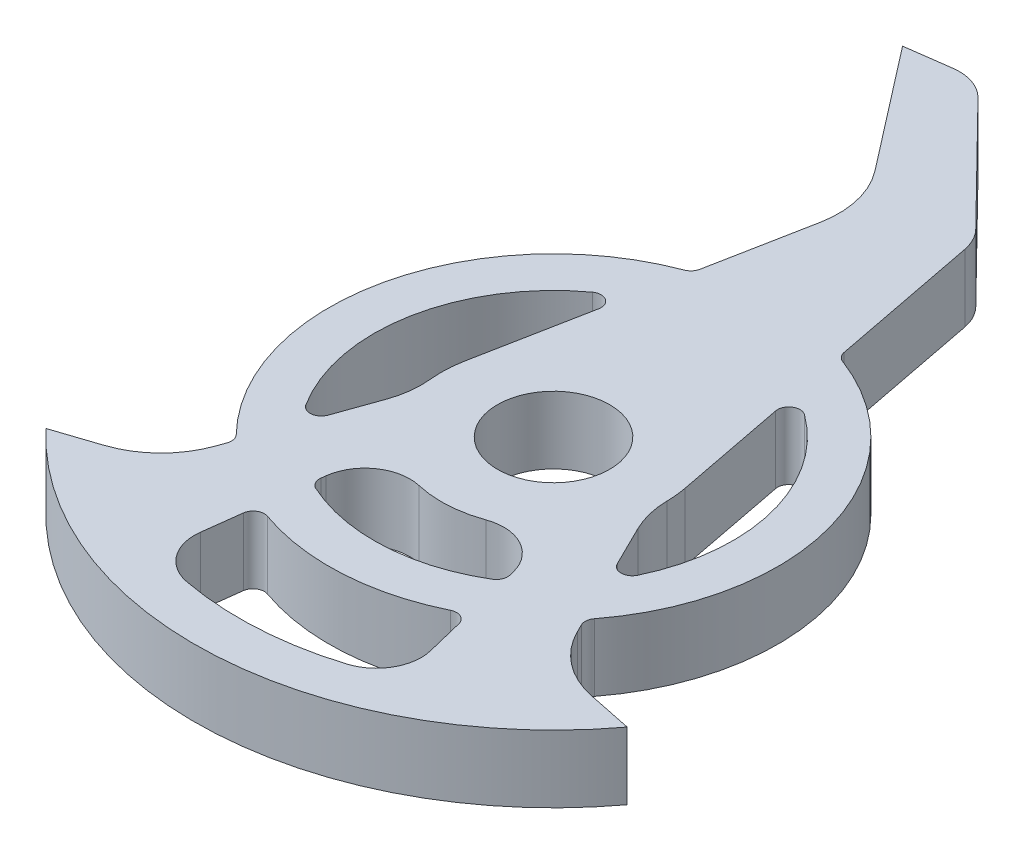
SolidWorks part; units mm, degrees
material "AISI Type A2 Tool Steel"
ref_plane "Front Plane" through (0, 0, 0) normal (0, 0, 1) x (1, 0, 0)
ref_plane "Top Plane" through (0, 0, 0) normal (0, 1, 0) x (1, 0, 0)
ref_plane "Right Plane" through (0, 0, 0) normal (1, 0, 0) x (0, 0, -1)
other "Center of Mass"
other "Bounding Box"
ref_plane "Default Plane" through (-8.9266, -12.7485, 0) normal (-0.1736, 0.9848, 0) x (0.9848, 0.1736, 0)
sketch "Sketch1" plane through (0, 0, 0) normal (0, 1, 0) x (1, 0, 0)
  line L0 (-15.5865, 3.0126) -> (-6.35, 50.8)
  line L1 (-6.35, 50.8) -> (-23.2013, 72.582)
  line L2 (15.5865, 3.0126) -> (6.35, 50.8)
  line L4 (-6.35, 50.8) -> (6.35, 50.8) construction
  line L5 (0, 50.8) -> (0, 0) construction
  line L6 (-23.2013, 72.582) -> (0, 0) construction
  line L7 (-23.2013, 72.582) -> (-13.7628, 73.8626)
  line L8 (-13.7628, 73.8626) -> (5.7363, 53.975)
  line L9 (5.7363, 53.975) -> (6.35, 50.8)
  circle A0 centre (0, 0) radius 7.9375
  arc A1 (-15.5865, 3.0126) -> (15.5865, 3.0126) centre (0, 0) ccw
  circle A2 centre (0, 0) radius 76.2 construction
  arc A4 (15.5865, 3.0126) -> (-15.5865, 3.0126) centre (0, 0) ccw construction
  dimension "D1" = 15.875
  dimension "D2" = 152.4
  dimension "D3" = 31.75
  dimension "D4" = 3.175
  dimension "D5" = 12.7
  dimension "D6" = 50.8
  dimension "D7" = 20
  dimension "D8" = 9.525
  dimension "D9" = 60
extrude "Boss-Extrude1" add sketch "Sketch1" along normal mid plane 9.525
fillet "Fillet6" radius 6.35 2 edges at (-13.7628, 0, -73.8626) (5.7363, 0, -53.975)
fillet "Fillet9" radius 12.7 1 edges at (-6.35, 0, -50.8)
sketch "Sketch4" plane through (0, 4.7625, 0) normal (0, 1, 0) x (1, 0, 0)
  circle A0 centre (0, 0) radius 31.75
  circle A1 centre (0, 0) radius 25.4
  dimension "D1" = 63.5
  dimension "D2" = 6.35
extrude "Boss-Extrude4" add sketch "Sketch4" against normal up to surface (9.525 mm away) up to face at (-6.3228, -4.7625, -45.9675)
sketch "Sketch2" plane through (0, 4.7625, 0) normal (0, 1, 0) x (1, 0, 0)
  line L0 (0, 0) -> (-1.4202, 24.3492) construction
  line L1 (-15.343, -4.0753) -> (-24.8926, -30.8684)
  line L2 (-24.8926, -30.8684) -> (-36.9477, -34.8642)
  line L3 (15.7127, -2.2639) -> (28.3126, -27.7651)
  line L4 (28.3126, -27.7651) -> (40.7504, -30.3323)
  line L5 (2.958, -50.7138) -> (0, 0) construction
  line L6 (-36.9477, -34.8642) -> (0, 0) construction
  line L7 (0, 0) -> (40.7504, -30.3323) construction
  line L8 (-36.9477, -34.8642) -> (1.9014, -32.5982) construction
  line L9 (1.9014, -32.5982) -> (40.7504, -30.3323) construction
  line L10 (-15.343, -4.0753) -> (15.7127, -2.2639) construction
  arc A0 (-15.5865, 3.0126) -> (15.5865, 3.0126) centre (0, 0) ccw construction
  arc A1 (-36.9477, -34.8642) -> (40.7504, -30.3323) centre (0, 0) ccw
  circle A2 centre (0, 0) radius 76.2 construction
  arc A3 (-15.343, -4.0753) -> (15.7127, -2.2639) centre (0, 0) ccw
  point P14 (-26.9073, -31.3896)
  dimension "D1" = 25.4
  dimension "D2" = 25
  dimension "D3" = 25
  dimension "D4" = 100
  dimension "D5" = 3.175
  dimension "D6" = 12.7
extrude "Boss-Extrude2" add sketch "Sketch2" against normal up to surface (9.525 mm away) up to face at (-6.3228, -4.7625, -47.2033)
sketch "Sketch3" plane through (0, 4.7625, 0) normal (0, 1, 0) x (1, 0, 0)
  line L0 (-10.2487, -12.1235) -> (-11.559, -22.6175)
  line L1 (11.5887, -10.8498) -> (14.1101, -21.1203)
  line L2 (-15.343, -4.0753) -> (-10.2487, -12.1235) construction
  line L3 (11.5887, -10.8498) -> (15.7127, -2.2639) construction
  line L4 (-15.343, -4.0753) -> (-19.6339, -16.1143) construction
  line L5 (-11.559, -22.6175) -> (-12.3852, -29.2347) construction
  line L6 (-12.3852, -29.2347) -> (-14.0024, -42.1869)
  line L7 (14.1101, -21.1203) -> (15.7, -27.5966) construction
  line L8 (15.7, -27.5966) -> (18.8121, -40.2729)
  arc A0 (11.5887, -10.8498) -> (-10.2487, -12.1235) centre (0, 0) cw
  arc A1 (-15.5865, 3.0126) -> (15.5865, 3.0126) centre (0, 0) ccw construction
  arc A2 (-14.0024, -42.1869) -> (18.8121, -40.2729) centre (0, 0) ccw
  arc A3 (-36.9477, -34.8642) -> (40.7504, -30.3323) centre (0, 0) ccw construction
  arc A4 (-11.559, -22.6175) -> (14.1101, -21.1203) centre (0, 0) ccw
  arc A5 (-12.3852, -29.2347) -> (15.7, -27.5966) centre (0, 0) ccw
  arc A6 (24.5449, -20.1397) -> (10.3685, 30.0093) centre (0, 0) ccw construction
  arc A7 (21.3742, -13.7224) -> (11.8238, 22.4802) centre (0, 0) ccw construction
  point P28 (23.5484, -37.6998)
  dimension "D1" = 6.35
  dimension "D2" = 12.5
  dimension "D3" = 9.525
extrude "Cut-Extrude1" cut sketch "Sketch3" against normal through all
fillet "Fillet7" radius 6.35 4 edges at (11.5887, 0, 10.8498) (-10.2487, 0, 12.1235) (18.8121, 0, 40.2729) (-14.0024, 0, 42.1869)
fillet "Fillet8" radius 12.7 4 edges at (28.3126, 0, 27.7651) (15.7127, 0, 2.2639) (-15.343, 0, 4.0753) (-24.8926, 0, 30.8684)
fillet "Fillet10" radius 1.5875 12 edges at (-11.559, 0, 22.6175) (-12.3852, 0, 29.2347) (15.7, 0, 27.5966) (24.5449, 0, 20.1397) (14.1101, 0, 21.1203) (21.3742, 0, 13.7224) (11.8238, 0, -22.4802) (10.3685, 0, -30.0093) (-11.8238, 0, -22.4802) (-10.3685, 0, -30.0093) (-19.6339, 0, 16.1143) (-22.0371, 0, 22.8567)
